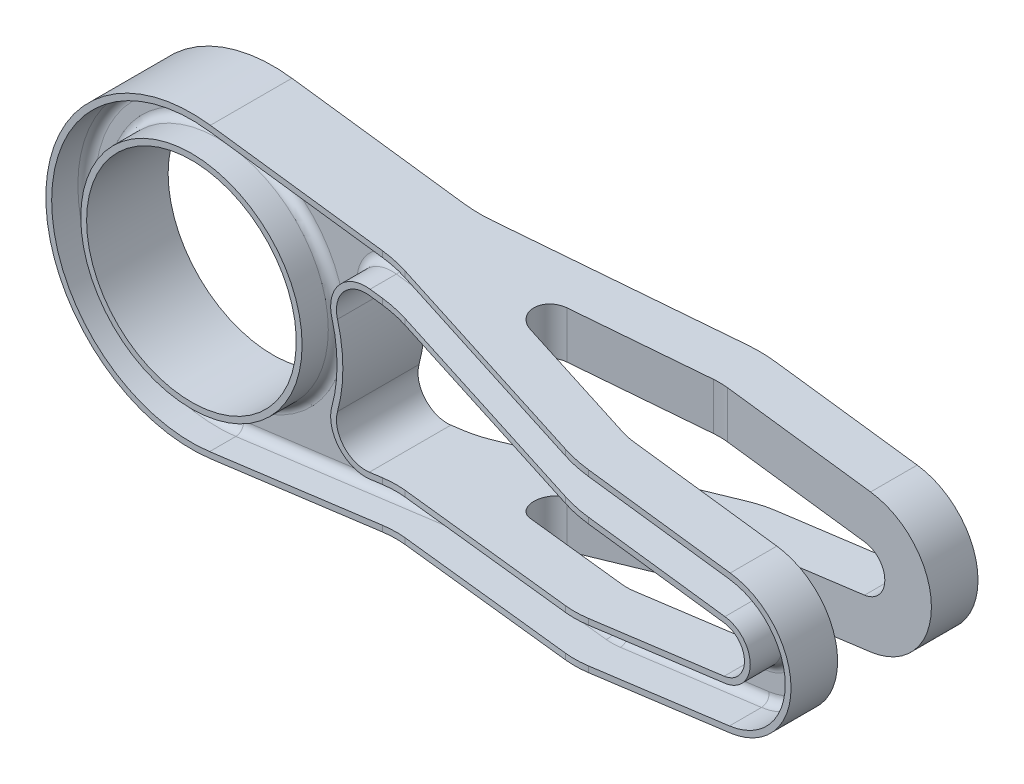
SolidWorks part; units mm, degrees
material "Molybdenum"
ref_plane "Front Plane" through (0, 0, 0) normal (0, 0, 1) x (1, 0, 0)
ref_plane "Top Plane" through (0, 0, 0) normal (0, 1, 0) x (1, 0, 0)
ref_plane "Right Plane" through (0, 0, 0) normal (1, 0, 0) x (0, 0, -1)
sketch "Sketch1" plane through (0, 0, 0) normal (0, 0, 1) x (1, 0, 0)
  line L0 (3.25, 24.7878) -> (101.56, 11.8982)
  line L1 (101.56, -11.8982) -> (3.25, -24.7878)
  line L2 (100, 0) -> (112, 0) construction
  line L3 (30.5507, 13.1399) -> (100.52, 3.9661)
  line L6 (100.52, -3.9661) -> (30.5507, -13.1399)
  circle A0 centre (0, 0) radius 18
  arc A2 (101.56, -11.8982) -> (101.56, 11.8982) centre (100, 0) ccw
  arc A3 (3.25, 24.7878) -> (3.25, -24.7878) centre (0, 0) ccw
  arc A4 (100.52, -3.9661) -> (100.52, 3.9661) centre (100, 0) ccw
  arc A7 (30.5507, -13.1399) -> (25.078, -6.8626) centre (29.9007, -8.1824) cw
  arc A8 (25.078, 6.8626) -> (30.5507, 13.1399) centre (29.9007, 8.1824) cw
  arc A9 (25.078, -6.8626) -> (25.078, 6.8626) centre (0, 0) ccw
  point P14 (21.7154, -14.2983)
  dimension "D1" = 25
  dimension "D2" = 36
  dimension "D3" = 8
  dimension "D4" = 12
  dimension "D6" = 8
  dimension "D7" = 5
  dimension "D5" = 100
  dimension "D8" = 8
  dimension "D9" = 8
extrude "1" add sketch "Sketch1" along normal blind 30
sketch "Sketch2" plane through (0, 0, 0) normal (0, 1, 0) x (1, 0, 0)
  line L0 (37.1794, 7.4932) -> (72.8206, 15.5579)
  line L1 (-25, 7) -> (32.7655, 7)
  line L2 (75.8938, 8.0511) -> (120, 8.0511) construction
  line L3 (54.322, 3.1699) -> (74.8041, 7.8045)
  line L4 (77.0111, 8.0511) -> (112, 8.0511)
  line L5 (77.2345, 16.0511) -> (112, 16.0511)
  line L6 (112, 16.0511) -> (112, 8.0511)
  line L7 (112, 16.0511) -> (112, 30.5161) construction
  line L8 (0, 0) -> (120.2315, 0) construction
  line L9 (112, -16.0511) -> (112, -8.0511)
  line L10 (-25, -1) -> (35.8938, -1) construction
  line L11 (120, 8.0511) -> (120, 30.5161) construction
  line L12 (77.2345, -16.0511) -> (112, -16.0511)
  line L13 (35, 7) -> (75, 16.0511) construction
  line L14 (75, 16.0511) -> (112, 16.0511) construction
  line L15 (-25, 7) -> (35, 7) construction
  line L16 (35.8938, -1) -> (75.8938, 8.0511) construction
  line L17 (77.0111, -8.0511) -> (112, -8.0511)
  line L18 (54.322, -3.1699) -> (74.8041, -7.8045)
  line L19 (-25, -7) -> (32.7655, -7)
  line L20 (37.1794, -7.4932) -> (72.8206, -15.5579)
  line L21 (-25, 0) -> (-25, -30) construction
  line L30 (-25, 7) -> (-25, -7)
  arc A0 (72.8206, 15.5579) -> (77.2345, 16.0511) centre (77.2345, -3.9489) cw
  arc A1 (32.7655, 7) -> (37.1794, 7.4932) centre (32.7655, 27) ccw
  arc A2 (74.8041, 7.8045) -> (77.0111, 8.0511) centre (77.0111, -1.9489) cw
  arc A3 (74.8041, -7.8045) -> (77.0111, -8.0511) centre (77.0111, 1.9489) ccw
  arc A4 (32.7655, -7) -> (37.1794, -7.4932) centre (32.7655, -27) cw
  arc A5 (72.8206, -15.5579) -> (77.2345, -16.0511) centre (77.2345, 3.9489) ccw
  arc A6 (54.322, -3.1699) -> (54.322, 3.1699) centre (55.0392, 0) cw
  point P19 (75, 16.0511)
  point P38 (35, -7)
  point P39 (35, 7)
  point P41 (75, -16.0511)
  dimension "D2" = 75
  dimension "D3" = 10
  dimension "D4" = 20
  dimension "D8" = 14
  dimension "D5" = 3.25
  dimension "D1" = 8
  dimension "D6" = 12.75
  dimension "D7" = 35
extrude "2" add sketch "Sketch2" along normal mid plane 50 separate body
combine bodies "3" operation type common bodies to combine 102 101
shell "4" thickness 1 removed face at (21.8126, 0, 7) removed face at (34.9793, -16.5935, 7.1851) removed face at (34.9793, 16.5935, 7.1851) removed face at (75.0207, -11.3436, 15.866) removed face at (75.0207, 11.3436, 15.866) removed face at (90.8773, 0, 16.0511) removed face at (55, -13.9685, 11.5255) removed face at (55, 13.9685, 11.5255)
fillet "5" radius 1.5 29 edges at (50.9085, -14.505, 1) (50.9085, 14.505, 1) (52.0566, 11.3288, 3.0276) (64.3423, 9.718, 6.4625) (75.7897, 8.2171, 8.9831) (88.8305, 6.5073, 9.0511) (105, 0, 9.0511) (88.8305, -6.5073, 9.0511) (75.7897, -8.2171, 8.9831) (64.3423, -9.718, 6.4625) (40.7946, 12.8054, 1) (25.3781, 12.1252, 1) (25, 0, 1) (25.3781, -12.1252, 1) (52.0566, -17.3801, 3.0276) (64.3423, -15.7693, 6.4625) (75.7897, -14.2684, 8.9831) (89.2205, -12.5075, 9.0511) (111, 0, 9.0511) (89.2205, 12.5075, 9.0511) (75.7897, 14.2684, 8.9831) (64.3423, 15.7693, 6.4625) (27.0143, -20.6635, 1) (-24, 0, 1) (19, 0, 1) (52.0566, -11.3288, 3.0276) (40.7946, -12.8054, 1) (52.0566, 17.3801, 3.0276) (27.0143, 20.6635, 1)
mirror "6" about plane through (0, 0, 0) normal (0, 0, 1) of bodies 103
ref_axis "Axis1" through (0, 0, 7) along (0, 0, -1)
